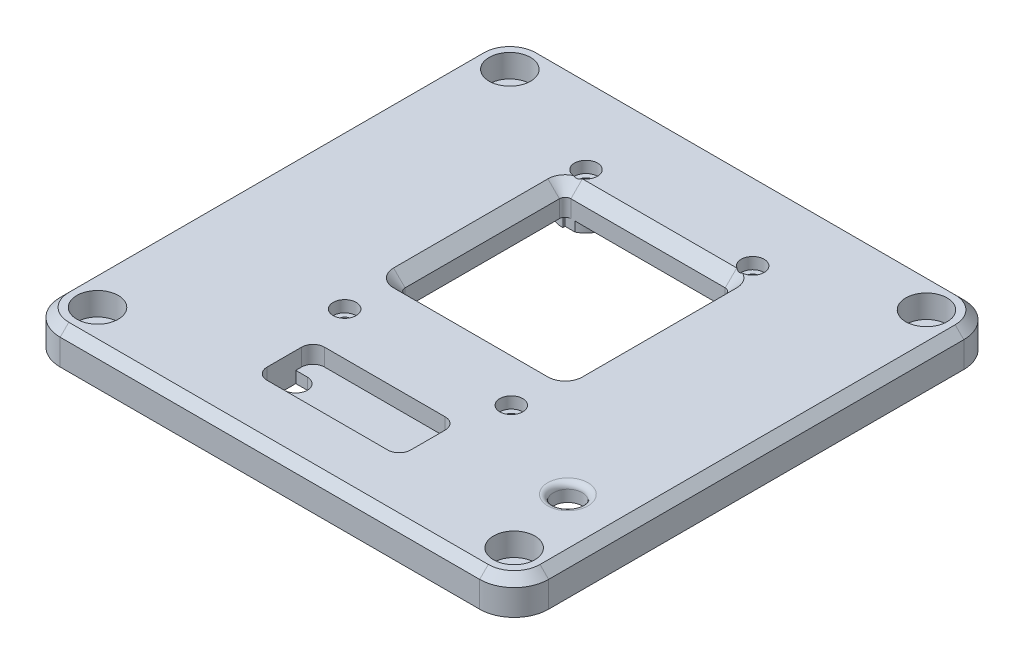
SolidWorks part; units mm, degrees
ref_plane "Front Plane" through (0, 0, 0) normal (0, 0, 1) x (1, 0, 0)
ref_plane "Top Plane" through (0, 0, 0) normal (0, 1, 0) x (1, 0, 0)
ref_plane "Right Plane" through (0, 0, 0) normal (1, 0, 0) x (0, 0, -1)
sketch "Sketch1" plane through (0, 0, 0) normal (0, 1, 0) x (1, 0, 0)
  line L0 (42.5, -42.125) -> (42.5, 42.125)
  line L1 (39.5, -39.125) -> (-39.5, -39.125)
  line L2 (39.5, -39.125) -> (39.5, 39.125)
  line L3 (39.5, 39.125) -> (-39.5, 39.125)
  line L4 (-39.5, -39.125) -> (-39.5, 39.125)
  line L5 (39.5, -39.125) -> (-39.5, 39.125) construction
  line L6 (39.5, 39.125) -> (-39.5, -39.125) construction
  line L7 (42.5, 42.125) -> (-42.5, 42.125)
  line L8 (-42.5, -42.125) -> (-42.5, 42.125)
  line L9 (42.5, -42.125) -> (-42.5, -42.125)
  point P0 (0, 0)
  dimension "D2" = 78.25
  dimension "D3" = 79
  dimension "D1" = 3
extrude "Boss-Extrude1" add sketch "Sketch1" along normal blind 3
extrude "Boss-Extrude2" add sketch "Sketch1<2>" along normal blind 3 from surface contours L9 L0 L7 L8 L1 L4 L3 L2 | L4 L1 L2 L3 region at (0, 0, 40.9282) region at (0, 0, 0) starting at face at (0, 3, 0)
sketch "Sketch1<2>" plane through (0, 0, 0) normal (0, 1, 0) x (1, 0, 0) same geometry as "Sketch1"
fillet "Fillet1" radius 3 4 edges at (39.5, 1.5, -39.125) (39.5, 1.5, 39.125) (-39.5, 1.5, -39.125) (-39.5, 1.5, 39.125)
fillet "Fillet2" radius 6 4 edges at (42.5, 3, 42.125) (42.5, 3, -42.125) (-42.5, 3, -42.125) (-42.5, 3, 42.125)
chamfer "Chamfer1" distance 1.5 angle 45 8 edges at (0, 6, -42.125) (40.7426, 6, -40.3676) (-40.7426, 6, -40.3676) (42.5, 6, 0) (-42.5, 6, 0) (40.7426, 6, 40.3676) (-40.7426, 6, 40.3676) (0, 6, 42.125)
sketch "Sketch3" plane through (0, 6, 0) normal (0, 1, 0) x (1, 0, 0)
  line L5 (-14.43, 23.68) -> (14.43, 23.68)
  line L6 (-14.43, 23.68) -> (-14.43, -5.18)
  line L7 (-14.43, -5.18) -> (14.43, -5.18)
  line L8 (14.43, 23.68) -> (14.43, -5.18)
  line L9 (-14.43, 23.68) -> (14.43, -5.18) construction
  line L10 (-14.43, -5.18) -> (14.43, 23.68) construction
  point P0 (0, 9.25)
  dimension "D1" = 28.86
  dimension "D2" = 28.86
  dimension "D3" = 9.25
extrude "Cut-Extrude1" cut sketch "Sketch3" against normal through all
fillet "Fillet3" radius 1 4 edges at (14.43, 4.5, 5.18) (-14.43, 4.5, 5.18) (-14.43, 4.5, -23.68) (14.43, 4.5, -23.68)
sketch "Sketch4" plane through (0, 3, 0) normal (0, -1, 0) x (1, 0, 0)
  line L0 (-14.43, 4.18) -> (-14.43, -22.68) construction
  line L1 (-13.43, -23.68) -> (13.43, -23.68) construction
  line L2 (14.43, -22.68) -> (14.43, 4.18) construction
  line L3 (13.43, 5.18) -> (-13.43, 5.18) construction
  line L4 (-14.43, 4.18) -> (-14.43, -22.68)
  line L5 (-13.43, -23.68) -> (13.43, -23.68)
  line L6 (14.43, -22.68) -> (14.43, 4.18)
  line L7 (13.43, 5.18) -> (-13.43, 5.18)
  line L8 (-17.43, 4.18) -> (-17.43, -22.68)
  line L9 (-13.43, -26.68) -> (13.43, -26.68)
  line L10 (17.43, -22.68) -> (17.43, 4.18)
  line L11 (13.43, 8.18) -> (-13.43, 8.18)
  arc A0 (-13.43, 5.18) -> (-14.43, 4.18) centre (-13.43, 4.18) ccw construction
  arc A1 (-14.43, -22.68) -> (-13.43, -23.68) centre (-13.43, -22.68) ccw construction
  arc A2 (13.43, -23.68) -> (14.43, -22.68) centre (13.43, -22.68) ccw construction
  arc A3 (14.43, 4.18) -> (13.43, 5.18) centre (13.43, 4.18) ccw construction
  arc A4 (-13.43, 5.18) -> (-14.43, 4.18) centre (-13.43, 4.18) ccw
  arc A5 (-14.43, -22.68) -> (-13.43, -23.68) centre (-13.43, -22.68) ccw
  arc A6 (13.43, -23.68) -> (14.43, -22.68) centre (13.43, -22.68) ccw
  arc A7 (14.43, 4.18) -> (13.43, 5.18) centre (13.43, 4.18) ccw
  arc A8 (-13.43, 8.18) -> (-17.43, 4.18) centre (-13.43, 4.18) ccw
  arc A9 (-17.43, -22.68) -> (-13.43, -26.68) centre (-13.43, -22.68) ccw
  arc A10 (13.43, -26.68) -> (17.43, -22.68) centre (13.43, -22.68) ccw
  arc A11 (17.43, 4.18) -> (13.43, 8.18) centre (13.43, 4.18) ccw
  dimension "D1" = 3
extrude "Boss-Extrude3" add sketch "Sketch4" along normal blind 2
chamfer "Chamfer2" distance 2 angle 45 8 edges at (0, 6, 5.18) (14.1371, 6, 4.8871) (-14.1371, 6, 4.8871) (14.43, 6, -9.25) (-14.43, 6, -9.25) (14.1371, 6, -23.3871) (-14.1371, 6, -23.3871) (0, 6, -23.68)
sketch "Sketch5" plane through (0, 6, 0) normal (0, 1, 0) x (1, 0, 0)
  line L1 (14.5, 27.38) -> (-14.5, 27.38) construction
  line L2 (14.5, 27.38) -> (14.5, -14.62) construction
  line L3 (14.5, -14.62) -> (-14.5, -14.62) construction
  line L4 (-14.5, 27.38) -> (-14.5, -14.62) construction
  line L5 (14.5, 27.38) -> (-14.5, -14.62) construction
  line L6 (14.5, -14.62) -> (-14.5, 27.38) construction
  circle A0 centre (-14.5, 27.38) radius 1.1
  circle A1 centre (14.5, 27.38) radius 1.1
  circle A2 centre (-14.5, -14.62) radius 1.1
  circle A3 centre (14.5, -14.62) radius 1.1
  point P0 (0, 6.38)
  dimension "D4" = 2.2
  dimension "D1" = 29
  dimension "D2" = 42
  dimension "D3" = 6.38
extrude "Cut-Extrude2" cut sketch "Sketch5" against normal through all
sketch "Sketch6" plane through (0, 3, 0) normal (0, -1, 0) x (1, 0, 0)
  line L0 (-13.43, -23.68) -> (13.43, -23.68) construction
  line L1 (-14.43, 5.18) -> (14.43, 5.18)
  line L2 (-14.43, 5.18) -> (-14.43, -23.68)
  line L3 (-14.43, -23.68) -> (14.43, -23.68)
  line L4 (14.43, 5.18) -> (14.43, -23.68)
  line L5 (-14.43, 5.18) -> (14.43, -23.68) construction
  line L6 (-14.43, -23.68) -> (14.43, 5.18) construction
  line L7 (-14.43, 4.18) -> (-14.43, -22.68) construction
  line L8 (13.43, 5.18) -> (-13.43, 5.18) construction
  arc A0 (-14.9543, -26.3782) -> (-13.6568, -26.6736) centre (-14.5, -27.38) ccw construction
  arc A1 (13.6568, -26.6736) -> (14.9543, -26.3782) centre (14.5, -27.38) ccw construction
  circle A2 centre (14.5, 14.62) radius 1.1 construction
  circle A3 centre (-14.5, 14.62) radius 1.1 construction
  circle A4 centre (-14.5, -27.38) radius 1.1
  circle A5 centre (14.5, -27.38) radius 1.1
  circle A6 centre (14.5, 14.62) radius 1.1
  circle A7 centre (-14.5, 14.62) radius 1.1
  circle A8 centre (-14.5, -27.38) radius 4.1
  circle A9 centre (14.5, -27.38) radius 4.1
  circle A10 centre (14.5, 14.62) radius 4.1
  circle A11 centre (-14.5, 14.62) radius 4.1
  arc A13 (-14.9543, -26.3782) -> (-13.6568, -26.6736) centre (-14.5, -27.38) ccw construction
  arc A14 (-16.1932, -23.646) -> (-11.3572, -24.7469) centre (-14.5, -27.38) ccw construction
  arc A15 (13.6568, -26.6736) -> (14.9543, -26.3782) centre (14.5, -27.38) ccw construction
  arc A16 (11.3572, -24.7469) -> (16.1932, -23.646) centre (14.5, -27.38) ccw construction
  point P32 (0, -9.25)
  circle M1 centre (14.5, 14.62) radius 1.1
  circle M2 centre (-14.5, 14.62) radius 1.1
  arc M3 (-13.6568, -26.6736) -> (-14.9543, -26.3782) centre (-14.5, -27.38) cw
  arc M4 (-14.9543, -26.3782) -> (-17.43, -22.68) centre (-13.43, -22.68) cw
  arc M10 (17.43, -22.68) -> (14.9543, -26.3782) centre (13.43, -22.68) cw
  arc M11 (14.9543, -26.3782) -> (13.6568, -26.6736) centre (14.5, -27.38) cw
  arc M12 (13.6568, -26.6736) -> (13.43, -26.68) centre (13.43, -22.68) cw
  line M13 (13.43, -26.68) -> (-13.43, -26.68)
  arc M14 (-13.43, -26.68) -> (-13.6568, -26.6736) centre (-13.43, -22.68) cw
  dimension "D1" = 3
extrude "Boss-Extrude4" add sketch "Sketch6" along normal blind 3.67 contours A10 M1 | A11 M2 | A8 M4 M13 M14 M3 | A8 L3 L2 A4 M13 M4 M14 | A9 L4 L3 A5 M10 M13 M12 | A9 M13 M10 M11 M12 region at (-13.7726, 3, -25.0889) region at (13.7726, 3, -25.0889) region at (-14.8427, 3, -28.4812) region at (14.8427, 3, -28.4812) region at (10.516, 3, 14.62) region at (-18.484, 3, 14.62)
sketch "Sketch7" plane through (0, 6, 0) normal (0, 1, 0) x (1, 0, 0)
  circle A0 centre (32.85, -23.13) radius 2.5
  dimension "D3" = 5
  dimension "D1" = 23.13
  dimension "D2" = 32.85
extrude "Cut-Extrude3" cut sketch "Sketch7" against normal through all
sketch "Sketch8" plane through (0, 6, 0) normal (0, 1, 0) x (1, 0, 0)
  circle A0 centre (-14.5, 27.38) radius 2
  circle A1 centre (14.5, 27.38) radius 2
  circle A2 centre (14.5, -14.62) radius 2
  circle A3 centre (-14.5, -14.62) radius 2
  dimension "D1" = 4
extrude "Cut-Extrude4" cut sketch "Sketch8" against normal blind 2
fillet "Fillet4" radius 1 1 edges at (32.85, 6, 25.63)
sketch "Sketch9" plane through (0, 6, 0) normal (0, 1, 0) x (1, 0, 0)
  line L0 (-42.5, -36.125) -> (-42.5, 36.125) construction
  line L1 (36.25, 35.875) -> (-36.25, 35.875) construction
  line L2 (36.25, 35.875) -> (36.25, -35.875) construction
  line L3 (36.25, -35.875) -> (-36.25, -35.875) construction
  line L4 (-36.25, 35.875) -> (-36.25, -35.875) construction
  line L5 (36.25, 35.875) -> (-36.25, -35.875) construction
  line L6 (36.25, -35.875) -> (-36.25, 35.875) construction
  line L7 (-36.5, 42.125) -> (36.5, 42.125) construction
  circle A0 centre (-36.25, 35.875) radius 2.05
  circle A1 centre (36.25, 35.875) radius 2.05
  circle A2 centre (36.25, -35.875) radius 2.05
  circle A3 centre (-36.25, -35.875) radius 2.05
  circle A4 centre (-36.25, 35.875) radius 3.6
  circle A5 centre (-36.25, -35.875) radius 3.6
  circle A6 centre (36.25, -35.875) radius 3.6
  circle A7 centre (36.25, 35.875) radius 3.6
  point P0 (0, 0)
  dimension "D3" = 4.1
  dimension "D4" = 7.2
  dimension "D1" = 6.25
  dimension "D2" = 6.25
extrude "Cut-Extrude5" cut sketch "Sketch9" against normal through all contours A0 | A2 | A3 | A1 region at (-36.25, 6, -35.875) region at (36.25, 6, 35.875) region at (-36.25, 6, 35.875)
extrude "Cut-Extrude6" cut sketch "Sketch9<3>" against normal blind 4
sketch "Sketch9<3>" plane through (0, 6, 0) normal (0, 1, 0) x (1, 0, 0) same geometry as "Sketch9"
sketch "Sketch10" plane through (0, 6, 0) normal (0, 1, 0) x (1, 0, 0)
  circle A0 centre (36.25, 35.875) radius 3.6 construction
  circle A1 centre (36.25, -35.875) radius 3.6 construction
  circle A2 centre (-36.25, -35.875) radius 3.6 construction
  circle A3 centre (-36.25, 35.875) radius 3.6 construction
  circle A4 centre (36.25, 35.875) radius 3.6
  circle A5 centre (36.25, -35.875) radius 3.6
  circle A6 centre (-36.25, -35.875) radius 3.6
  circle A7 centre (-36.25, 35.875) radius 3.6
  circle A8 centre (36.25, 35.875) radius 6.25
  circle A9 centre (36.25, -35.875) radius 6.25
  circle A10 centre (-36.25, -35.875) radius 6.25
  circle A11 centre (-36.25, 35.875) radius 6.25
  circle A12 centre (-36.25, -35.875) radius 2.05 construction
  circle A13 centre (-36.25, -35.875) radius 2.05
  circle A14 centre (36.25, -35.875) radius 2.05 construction
  circle A15 centre (36.25, -35.875) radius 2.05
  circle A16 centre (-36.25, 35.875) radius 2.05 construction
  circle A17 centre (-36.25, 35.875) radius 2.05
  circle A18 centre (36.25, 35.875) radius 2.05 construction
  circle A19 centre (36.25, 35.875) radius 2.05
  circle M4 centre (36.25, 35.875) radius 3.6
  circle M5 centre (36.25, -35.875) radius 3.6
  circle M6 centre (-36.25, -35.875) radius 3.6
  circle M7 centre (-36.25, 35.875) radius 3.6
  arc M23 (41, 36.125) -> (36.5, 40.625) centre (36.5, 36.125) ccw
  line M24 (36.5, 40.625) -> (-36.5, 40.625)
  arc M25 (-36.5, 40.625) -> (-41, 36.125) centre (-36.5, 36.125) ccw
  line M26 (-41, 36.125) -> (-41, -36.125)
  arc M27 (-41, -36.125) -> (-36.5, -40.625) centre (-36.5, -36.125) ccw
  line M28 (-36.5, -40.625) -> (36.5, -40.625)
  arc M29 (36.5, -40.625) -> (41, -36.125) centre (36.5, -36.125) ccw
  line M30 (41, -36.125) -> (41, 36.125)
  dimension "D1" = 12.5
extrude "Boss-Extrude7" add sketch "Sketch10" against normal blind 1 from surface contours A11 M26 M24 M25 M7 | A8 M24 M30 M23 M4 | A9 M30 M28 M29 M5 | A10 M28 M26 M27 M6 region at (34.344, 6, -40.4694) region at (-30.7146, 6, -38.4248) region at (40.8444, 6, 33.969) region at (-34.1388, 6, 30.1579) starting at face at (0, 3, 0)
extrude "Boss-Extrude8" add sketch "Sketch10<4>" against normal up to surface (6 mm away) from surface contours A13 M6 | A15 M5 | A17 M7 | A19 M4 | A8 M24 M30 M23 M4 | A9 M30 M28 M29 M5 | A10 M28 M26 M27 M6 | A11 M26 M24 M25 M7 region at (32.7518, 6, -35.875) region at (32.7518, 6, 35.875) region at (-39.7482, 6, 35.875) region at (-39.7482, 6, -35.875) region at (34.344, 6, -40.4694) region at (-30.7146, 6, -38.4248) region at (40.8444, 6, 33.969) region at (-34.1388, 6, 30.1579) up to face at (0, 0, 0) starting at face at (34.4604, 2, -34.0854)
sketch "Sketch10<4>" plane through (0, 6, 0) normal (0, 1, 0) x (1, 0, 0) same geometry as "Sketch10"
sketch "Sketch11" plane through (0, 6, 0) normal (0, 1, 0) x (1, 0, 0)
  line L0 (36.5, -42.125) -> (-36.5, -42.125) construction
  line L1 (-12.5, -22.125) -> (12.5, -22.125)
  line L2 (-12.5, -22.125) -> (-12.5, -32.125)
  line L3 (-12.5, -32.125) -> (12.5, -32.125)
  line L4 (12.5, -22.125) -> (12.5, -32.125)
  line L5 (-12.5, -22.125) -> (12.5, -32.125) construction
  line L6 (-12.5, -32.125) -> (12.5, -22.125) construction
  point P0 (0, -27.125)
  point P5 (0, 0)
  dimension "D1" = 25
  dimension "D2" = 10
  dimension "D3" = 15
extrude "Cut-Extrude7" cut sketch "Sketch11" against normal blind 3
sketch "Sketch12" plane through (0, 3, 0) normal (0, -1, 0) x (1, 0, 0)
  line L0 (12.5, 32.125) -> (12.5, 22.125) construction
  line L1 (-12.5, 32.125) -> (12.5, 32.125) construction
  line L2 (-12.5, 22.125) -> (-12.5, 32.125) construction
  line L3 (12.5, 22.125) -> (-12.5, 22.125) construction
  line L4 (12.5, 32.125) -> (12.5, 22.125)
  line L5 (-12.5, 32.125) -> (12.5, 32.125)
  line L6 (-12.5, 22.125) -> (-12.5, 32.125)
  line L7 (12.5, 22.125) -> (-12.5, 22.125)
  line L8 (15.5, 35.125) -> (15.5, 19.125)
  line L9 (15.5, 19.125) -> (-15.5, 19.125)
  line L10 (-15.5, 19.125) -> (-15.5, 35.125)
  line L11 (-15.5, 35.125) -> (15.5, 35.125)
  line L13 (-8.5, 25.125) -> (-12.5, 25.125)
  line L14 (-8.5, 25.125) -> (-8.5, 29.125)
  line L15 (-8.5, 29.125) -> (-12.5, 29.125)
  line L16 (-12.5, 25.125) -> (-12.5, 29.125)
  line L17 (-8.5, 25.125) -> (-12.5, 29.125) construction
  line L18 (-8.5, 29.125) -> (-12.5, 25.125) construction
  point P8 (-10.5, 27.125)
  point P13 (0, 0)
  point P14 (12.5, 27.125)
  line M9 (12.5, 32.125) -> (12.5, 22.125)
  line M10 (12.5, 22.125) -> (-12.5, 22.125)
  line M11 (-12.5, 22.125) -> (-12.5, 32.125)
  line M12 (-12.5, 32.125) -> (12.5, 32.125)
  dimension "D1" = 3
  dimension "D2" = 4
  dimension "D3" = 4
extrude "Boss-Extrude9" add sketch "Sketch12" along normal blind 2 contours L15 L14 L13 M11 M10 M9 M12 | L11 L10 L9 L8 L6 M12 M9 M10 M11 region at (0.7179, 3, 27.125) region at (15.1511, 3, 27.125)
fillet "Fillet5" radius 2 6 edges at (-8.5, 2, 29.125) (-8.5, 2, 25.125) (-12.5, 4.5, 32.125) (12.5, 4.5, 32.125) (12.5, 4.5, 22.125) (-12.5, 4.5, 22.125)
